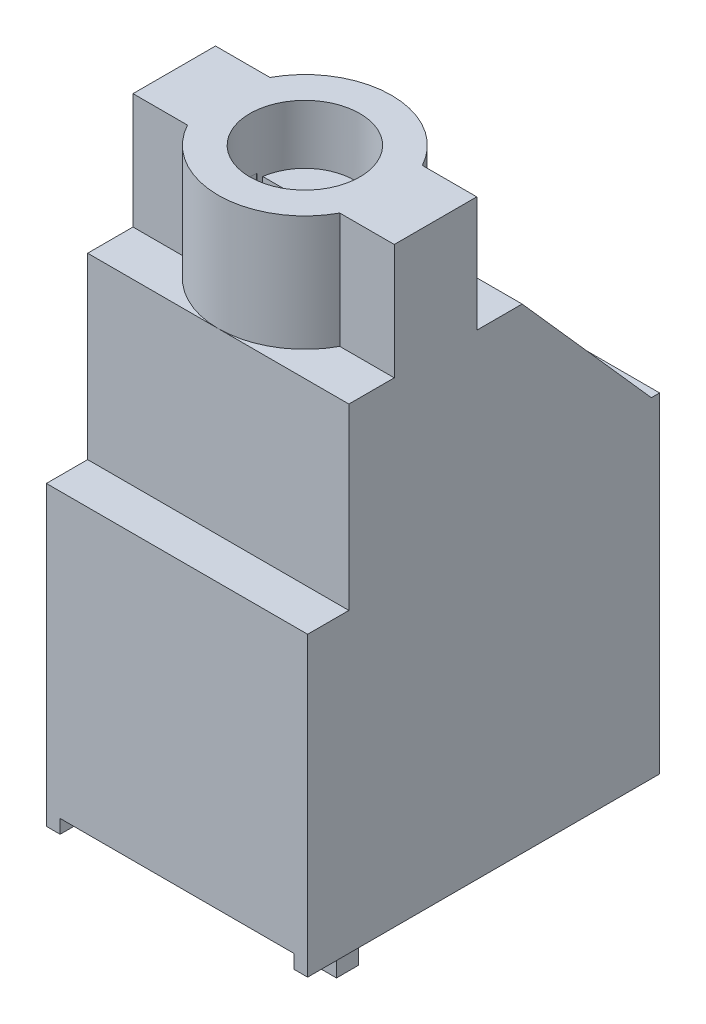
SolidWorks part; units mm, degrees
material "ABS"
ref_plane "前视基准面" through (0, 0, 0) normal (0, 0, 1) x (1, 0, 0)
ref_plane "上视基准面" through (0, 0, 0) normal (0, 1, 0) x (1, 0, 0)
ref_plane "右视基准面" through (0, 0, 0) normal (1, 0, 0) x (0, 0, -1)
sketch "草图2" plane through (0, 0, 0) normal (1, 0, 0) x (0, 0, -1)
  line L0 (6.4, 0) -> (-6.4, 0)
  line L1 (-6.4, 0) -> (-6.4, 10.8)
  line L2 (-6.4, 10.8) -> (-4.9, 10.8)
  line L3 (-4.9, 10.8) -> (-4.9, 17.3)
  line L4 (-4.9, 17.3) -> (-3.25, 17.3)
  line L5 (-3.25, 17.3) -> (-3.25, 21.5)
  line L6 (-3.25, 21.5) -> (-0.25, 21.5)
  line L7 (-0.25, 21.5) -> (-0.25, 17.3)
  line L8 (6.1, 12) -> (1.4, 17.3)
  line L9 (6.1, 12) -> (6.4, 12)
  line L10 (6.4, 12) -> (6.4, 0)
  line L11 (0, 82.2465) -> (0, -29.6489) construction
  line L12 (1.4, 17.3) -> (-0.25, 17.3)
  line L13 (-1.75, 24.1268) -> (-1.75, 14.5128) construction
  dimension "D1" = 12.8
  dimension "D2" = 21.5
  dimension "D3" = 3
  dimension "D4" = 1.5
  dimension "D5" = 4.2
  dimension "D6" = 10.8
  dimension "D7" = 12
  dimension "D8" = 6.3
  dimension "D9" = 0.3
extrude "凸台-拉伸1" add sketch "草图2" along normal blind 4.75 and the other way blind 4.75
sketch "草图3" plane through (0, 21.5, 0) normal (0, 1, 0) x (1, 0, 0)
  line L0 (-8.5326, -1.75) -> (7.6987, -1.75) construction
  line L1 (-4.75, 1.4) -> (4.75, 1.4) construction
  line L2 (-4.75, -4.9) -> (4.75, -4.9) construction
  line L3 (0, 8.5645) -> (0, -8.8898) construction
  line L4 (-4.75, -4.9) -> (4.75, -4.9) construction
  circle A0 centre (0, -1.75) radius 3.15
extrude "凸台-拉伸2" add sketch "草图3" against normal up to next (21.5 mm away)
sketch "草图4" plane through (0, 21.5, 0) normal (0, 1, 0) x (1, 0, 0)
  circle A0 centre (0, -1.75) radius 2
  arc A1 (2.7699, -0.25) -> (0, 1.4) centre (0, -1.75) ccw construction
  dimension "D1" = 4
extrude "切除-拉伸1" cut sketch "草图4" against normal blind 2
sketch "草图7" plane through (0, 19.5, 0) normal (0, 1, 0) x (1, 0, 0)
  circle A1 centre (0, -1.75) radius 2 construction
  circle A2 centre (0, -1.75) radius 2
  circle A3 centre (0, -1.75) radius 1.8
  dimension "D1" = 0.2
extrude "切除-拉伸5" cut sketch "草图7" against normal blind 0.5
sketch "草图5" plane through (0, 19.5, 0) normal (0, 1, 0) x (1, 0, 0)
  line L0 (2.9198, -1.75) -> (-3.0795, -1.75) construction
  line L1 (-2, -1.5) -> (2, -1.5)
  line L2 (-2, -1.5) -> (-2, -2)
  line L3 (-2, -2) -> (2, -2)
  line L4 (2, -1.5) -> (2, -2)
  line L5 (0, 1.1079) -> (0, -1.2643) construction
  line L10 (-4.75, 1.4) -> (0, 1.4) construction
  line L11 (-4.75, -4.9) -> (4.75, -4.9) construction
  circle A0 centre (0, -1.75) radius 2 construction
  dimension "D1" = 0.5
extrude "切除-拉伸2" cut sketch "草图5" against normal blind 0.5
sketch "草图8" plane through (0, 0, -6.4) normal (0, 0, -1) x (-1, 0, 0)
  line L0 (0, -8.4917) -> (0, 27.7719) construction
  line L1 (4.75, 0) -> (-4.75, 0) construction
  line L2 (-1.75, 9) -> (1.75, 9)
  line L3 (-1.75, 9) -> (-1.75, 4.5)
  line L4 (-1.75, 4.5) -> (1.75, 4.5)
  line L5 (1.75, 9) -> (1.75, 4.5)
  dimension "D1" = 4.5
  dimension "D2" = 3.5
  dimension "D3" = 4.5
extrude "切除-拉伸6" cut sketch "草图8" against normal blind 2
chamfer "倒角1" distance 1 angle 60 4 edges at (0, 9, -6.4) (-1.75, 6.75, -6.4) (1.75, 6.75, -6.4) (0, 4.5, -6.4) first distance on face at (0, 6.75, -6.4)
sketch "草图9" plane through (0, 0, 0) normal (0, -1, 0) x (1, 0, 0)
  line L0 (-4.75, 6.4) -> (4.75, 6.4) construction
  line L1 (-4.25, 6.4) -> (4.25, 6.4)
  line L2 (-4.25, 6.4) -> (-4.25, -6.4)
  line L3 (-4.25, -6.4) -> (4.25, -6.4)
  line L4 (4.25, 6.4) -> (4.25, -6.4)
  line L5 (-4.75, -6.4) -> (4.75, -6.4) construction
  line L6 (0, 11.6522) -> (0, -12.157) construction
  line L7 (-4.75, 6.4) -> (-4.75, -6.4) construction
  line L8 (4.75, 6.4) -> (4.75, -6.4) construction
  point P10 (-4.75, 0)
  dimension "D1" = 0.5
  dimension "D2" = 0.5
extrude "切除-拉伸7" cut sketch "草图9" against normal blind 0.5
sketch "草图10" plane through (0, 0.5, 0) normal (0, -1, 0) x (1, 0, 0)
  line L0 (0, 2.8369) -> (0, -1.126) construction
  line L1 (-0.6, 1.2) -> (0.6, 1.2)
  line L2 (-0.6, 1.2) -> (-0.6, 0.4)
  line L3 (-0.6, 0.4) -> (0.6, 0.4)
  line L4 (0.6, 1.2) -> (0.6, 0.4)
  line L5 (-1.1133, 0.8) -> (0.9224, 0.8) construction
  line L6 (4.25, 6.4) -> (-4.25, 6.4) construction
  dimension "D1" = 1.2
  dimension "D2" = 0.8
  dimension "D3" = 5.6
extrude "凸台-拉伸4" add sketch "草图10" along normal blind 5.2
